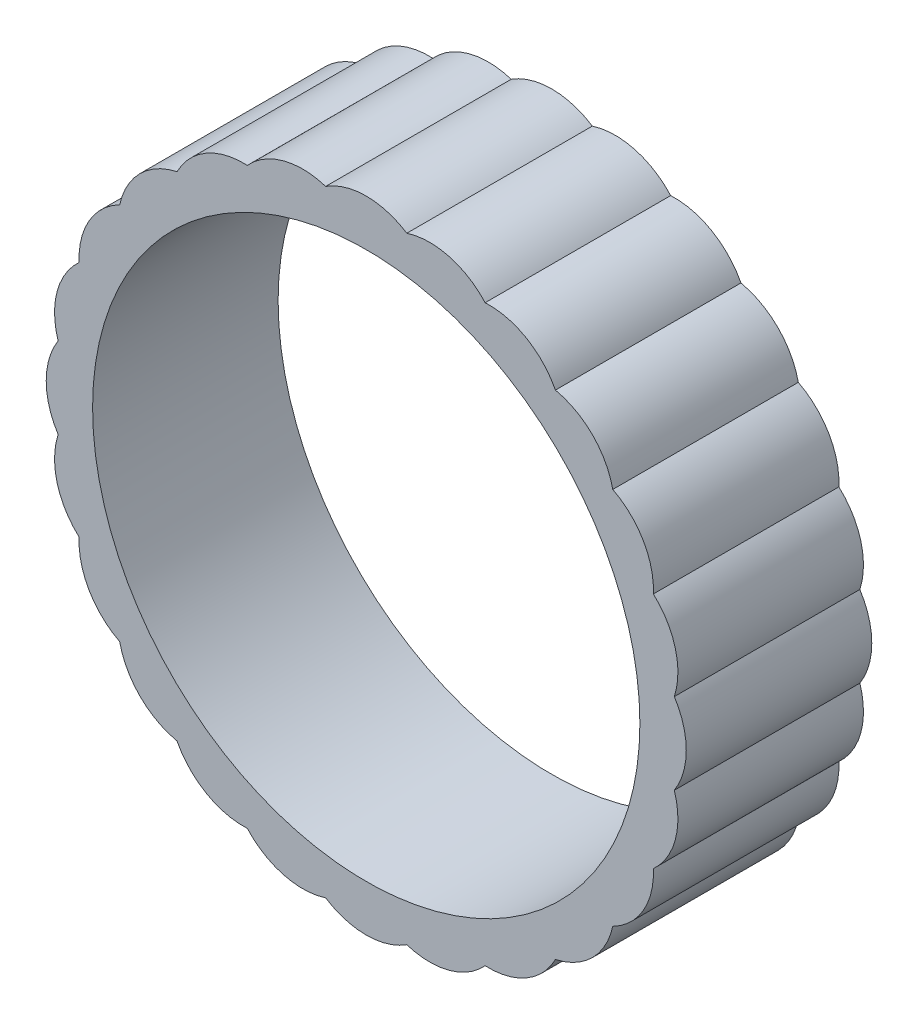
SolidWorks part; units mm, degrees
ref_plane "Front Plane" through (0, 0, 0) normal (0, 0, 1) x (1, 0, 0)
ref_plane "Top Plane" through (0, 0, 0) normal (0, 1, 0) x (1, 0, 0)
ref_plane "Right Plane" through (0, 0, 0) normal (1, 0, 0) x (0, 0, -1)
sketch "Sketch1" plane through (0, 0, 0) normal (0, 0, 1) x (1, 0, 0)
  circle A0 centre (0, 0) radius 16.75
  circle A1 centre (0, 0) radius 14.75
  dimension "D1" = 29.5
  dimension "D2" = 2
extrude "Boss-Extrude1" add sketch "Sketch1" along normal blind 10
sketch "Sketch2" plane through (0, 0, 10) normal (0, 0, 1) x (1, 0, 0)
  line L0 (0, 16.75) -> (1.1603, 16.75) construction
  line L2 (0, 17.25) -> (1.2638, 17.25) construction
  arc A0 (-2.1863, 16.6067) -> (2.1863, 16.6067) centre (0, 13.2131) cw
  circle A1 centre (0, 0) radius 16.75 construction
  arc A2 (2.1863, 16.6067) -> (-2.1863, 16.6067) centre (0, 0) ccw
  dimension "D1" = 15
  dimension "D2" = 0.5
extrude "Boss-Extrude2" add sketch "Sketch2" against normal blind 10
pattern_circular "CirPattern1" count 24 over 360 about axis through (0, 0, 10) along (0, 0, 1) of "Boss-Extrude2"
